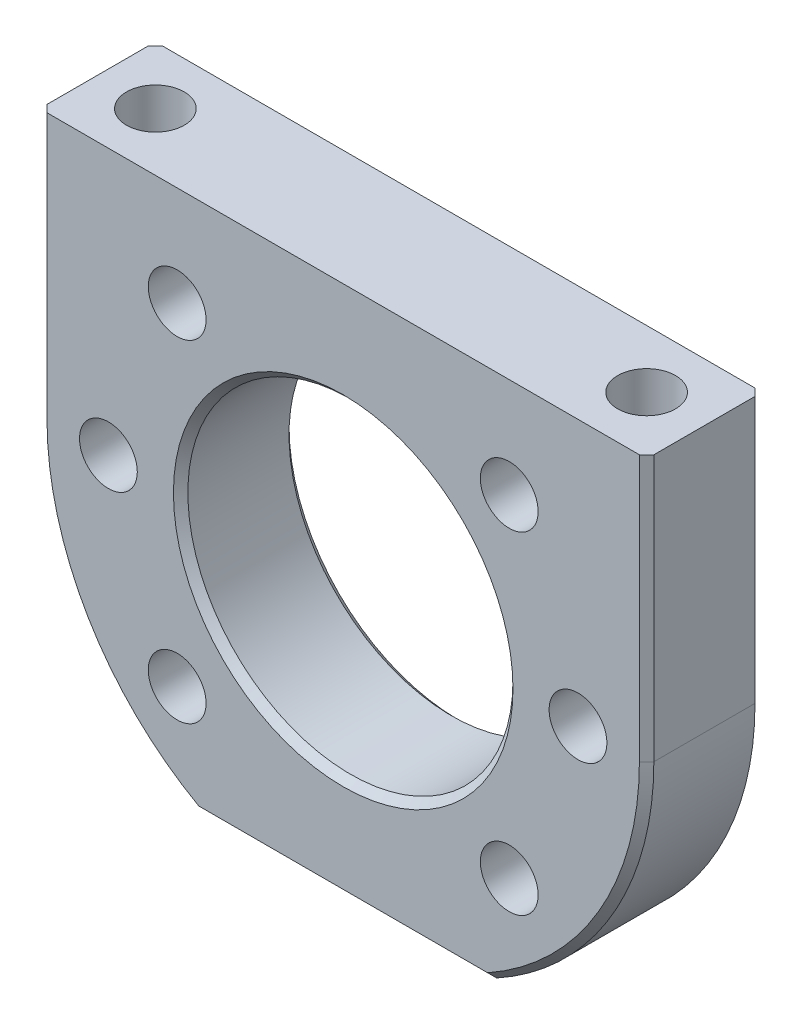
SolidWorks part; units mm, degrees
ref_plane "Front Plane" through (0, 0, 0) normal (0, 0, 1) x (1, 0, 0)
ref_plane "Top Plane" through (0, 0, 0) normal (0, 1, 0) x (1, 0, 0)
ref_plane "Right Plane" through (0, 0, 0) normal (1, 0, 0) x (0, 0, -1)
sketch "Sketch1" plane through (0, 0, 0) normal (0, 0, 1) x (1, 0, 0)
  line L0 (21, 0) -> (21, 18.4)
  line L3 (-10.1213, -18.4) -> (10.1213, -18.4)
  line L4 (-21, 0) -> (-21, 18.4)
  line L5 (-21, 18.4) -> (21, 18.4)
  arc A0 (10.1213, -18.4) -> (21, 0) centre (0, 0) ccw
  arc A1 (-21, 0) -> (-10.1213, -18.4) centre (0, 0) ccw
  dimension "D1" = 21
  dimension "D4" = 21
  dimension "D2" = 21
  dimension "D3" = 18.4
  dimension "D5" = 36.8
extrude "Boss-Extrude1" add sketch "Sketch1" along normal mid plane 8
sketch "Sketch2" plane through (0, 0, 4) normal (0, 0, 1) x (1, 0, 0)
  circle A0 centre (0, 0) radius 11.25
  dimension "D1" = 22.5
extrude "Cut-Extrude1" cut sketch "Sketch2" against normal through all
sketch "Sketch3" plane through (0, 0, 4) normal (0, 0, 1) x (1, 0, 0)
  line L0 (0, 21) -> (0, -21) construction
  line L1 (0, 0) -> (-19.8057, 19.8057) construction
  line L2 (0, 0) -> (19.0248, 19.0248) construction
  circle A0 centre (-16.25, 0) radius 2
  circle A1 centre (16.25, 0) radius 2
  circle A2 centre (0, 0) radius 16.25 construction
  circle A3 centre (-11.4905, 11.4905) radius 2
  circle A5 centre (11.4905, 11.4905) radius 2
  circle A6 centre (11.4905, -11.4905) radius 2
  circle A8 centre (-11.4905, -11.4905) radius 2
  dimension "D3" = 32.5
  dimension "D4" = 4
  dimension "D5" = 4
  dimension "D6" = 4
  dimension "D7" = 4
  dimension "D8" = 4
  dimension "D9" = 4
  dimension "D1" = 45
  dimension "D2" = 45
extrude "Cut-Extrude2" cut sketch "Sketch3" against normal blind 8
sketch "Sketch6" plane through (-3.375, 18.4, 0) normal (0, -1, 0) x (0, 0, -1)
  line L0 (0, -996.625) -> (0, 49003.375) construction
  circle A0 centre (0, -13.625) radius 2
  circle A1 centre (0, 20.375) radius 2
  dimension "D1" = 17
  dimension "D2" = 17
  dimension "D3" = 4
  dimension "D4" = 4
extrude "Cut-Extrude3" cut sketch "Sketch6" along normal blind 8
chamfer "Chamfer1" distance 0.5 angle 45 12 edges at (11.25, 0, -4) (-21, 9.2, 4) (-18.0769, -10.6877, 4) (0, -18.4, 4) (18.0769, -10.6877, 4) (21, 9.2, 4) (-21, 9.2, -4) (-18.0769, -10.6877, -4) (0, -18.4, -4) (18.0769, -10.6877, -4) (21, 9.2, -4) (11.25, 0, 4)
equation "\"D6@Sketch3\"=\"D5@Sketch3\""
equation "\"D9@Sketch3\"=\"D5@Sketch3\""
equation "\"D8@Sketch3\"=\"D5@Sketch3\""
equation "\"D7@Sketch3\"=\"D5@Sketch3\""
equation "\"D4@Sketch3\"=\"D5@Sketch3\""
equation "\"D1@Sketch6\"=34/2"
equation "\"D4@Sketch6\"=\"D3@Sketch6\""
equation "\"D3@Sketch1\"=\"D5@Sketch1\"/2"
equation "\"D2@Sketch6\"=\"D1@Sketch6\""
